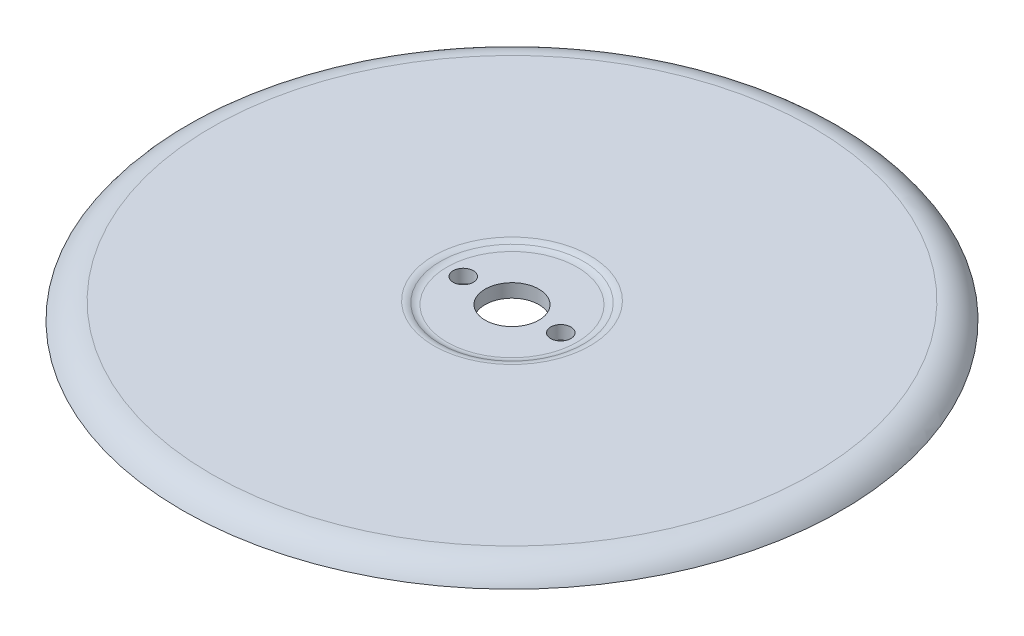
SolidWorks part; units mm, degrees
ref_plane "Alzado" through (0, 0, 0) normal (0, 0, 1) x (1, 0, 0)
ref_plane "Planta" through (0, 0, 0) normal (0, 1, 0) x (1, 0, 0)
ref_plane "Vista lateral" through (0, 0, 0) normal (1, 0, 0) x (0, 0, -1)
sketch "Croquis1" plane through (0, 0, 0) normal (0, 1, 0) x (1, 0, 0)
  line L0 (0, 0) -> (7.25, 0) construction
  line L1 (0, -55) -> (0, 55) construction
  circle A0 centre (0, 0) radius 49
  circle A1 centre (0, 0) radius 4
  circle A2 centre (7.25, 0) radius 1.5
  circle A3 centre (-7.25, 0) radius 1.5
  dimension "D1" = 98
  dimension "D3" = 8
  dimension "D4" = 3
  dimension "D2" = 7.25
extrude "Saliente-Extruir1" add sketch "Croquis1" along normal blind 2.5
sketch "Croquis2" plane through (0, 2.5, 0) normal (0, 1, 0) x (1, 0, 0)
  circle A0 centre (0, 0) radius 11
  dimension "D1" = 22
extrude "Cortar-Extruir1" cut sketch "Croquis2" against normal blind 0.5
fillet "Redondeo1" radius 2 1 edges at (0, 2, 11)
fillet "Redondeo2" radius 2 1 edges at (0, 2.5, 11)
fillet "Redondeo3" radius 5 1 edges at (0, 2.5, 49)
